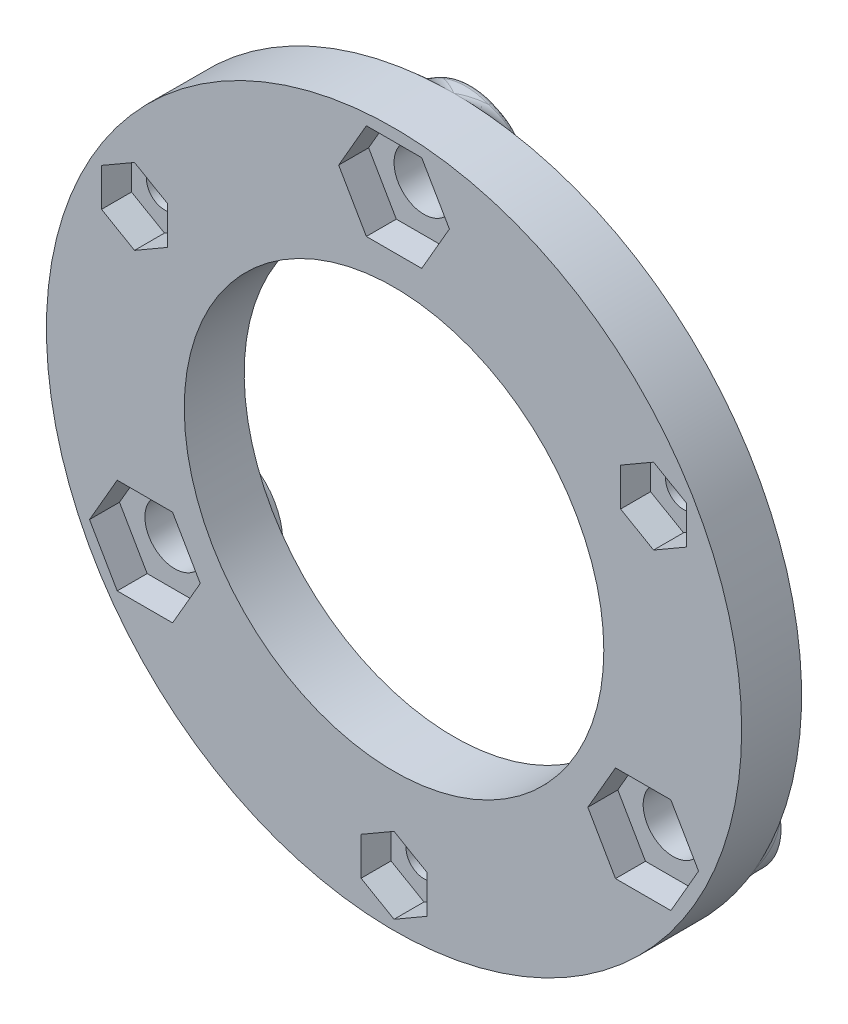
SolidWorks part; units mm, degrees
ref_plane "Front Plane" through (0, 0, 0) normal (0, 0, 1) x (1, 0, 0)
ref_plane "Top Plane" through (0, 0, 0) normal (0, 1, 0) x (1, 0, 0)
ref_plane "Right Plane" through (0, 0, 0) normal (1, 0, 0) x (0, 0, -1)
sketch "Sketch2" plane through (0, 0, 0) normal (0, 0, 1) x (1, 0, 0)
  line L0 (0, 24) -> (0, 0) construction
  line L1 (0, 0) -> (21.6506, 12.5) construction
  circle A0 centre (0, 0) radius 29
  circle A1 centre (0, 0) radius 17.5
  circle A2 centre (0, 0) radius 24 construction
  circle A3 centre (0, 24) radius 2.5
  circle A4 centre (0, 0) radius 25 construction
  circle A5 centre (20.7846, -12) radius 2.5
  circle A8 centre (21.6506, 12.5) radius 1.5
  circle A9 centre (0, -25) radius 1.5
  circle A11 centre (0, 0) radius 8 construction
  circle A14 centre (0, 24) radius 5 construction
  circle A15 centre (0, 0) radius 19 construction
  circle A16 centre (-20.7846, -12) radius 2.5
  circle A19 centre (-21.6506, 12.5) radius 1.5
  point P17 (0, 0)
  point P24 (0, 0)
  dimension "D1" = 58
  dimension "D2" = 48
  dimension "D4" = 5
  dimension "D7" = 3
  dimension "D3" = 16
  dimension "D10" = 10
  dimension "D5" = 4
  dimension "D9" = 1.5
  dimension "D11" = 60
  dimension "D6" = 3
  dimension "D8" = 3
extrude "Boss-Extrude1" add sketch "Sketch2" along normal blind 5
sketch "Sketch3" plane through (0, 0, 5) normal (0, 0, 1) x (1, 0, 0)
  line L0 (0, 24) -> (0, 0) construction
  line L13 (-4.6188, 24) -> (-2.3094, 20)
  line L14 (-2.3094, 20) -> (2.3094, 20)
  line L15 (2.3094, 20) -> (4.6188, 24)
  line L16 (4.6188, 24) -> (2.3094, 28)
  line L17 (2.3094, 28) -> (-2.3094, 28)
  line L18 (-2.3094, 28) -> (-4.6188, 24)
  line L20 (21.6506, 9.3246) -> (24.4006, 10.9123)
  line L21 (24.4006, 10.9123) -> (24.4006, 14.0877)
  line L22 (24.4006, 14.0877) -> (21.6506, 15.6754)
  line L23 (21.6506, 15.6754) -> (18.9006, 14.0877)
  line L24 (18.9006, 14.0877) -> (18.9006, 10.9123)
  line L25 (18.9006, 10.9123) -> (21.6506, 9.3246)
  circle A0 centre (0, 24) radius 4 construction
  circle A1 centre (21.6506, 12.5) radius 2.75 construction
  dimension "D1" = 8
  dimension "D2" = 5.5
extrude "Cut-Extrude1" cut sketch "Sketch3" against normal blind 2.5
pattern_circular "CirPattern1" count 3 over 360 about axis through (0, 0, 5) along (0, 0, -1) of "Cut-Extrude1" reverse direction yes
sketch "Sketch4" plane through (0, 0, 0) normal (0, 0, -1) x (-1, 0, 0)
  circle A0 centre (0, 24) radius 4
  circle A1 centre (0, 24) radius 5
  dimension "D1" = 8
extrude "Boss-Extrude2" add sketch "Sketch4" along normal blind 1.5
fillet "Fillet1" radius 1.5 1 edges at (-5, 24, 0)
fillet "Fillet2" radius 0.5 2 edges at (0, 29, -1.5) (0, 19, -1.5)
chamfer "Chamfer1" distance 0.25 angle 45 1 edges at (-4, 24, -1.5)
pattern_circular "CirPattern2" count 3 over 360 about axis through (0, 0, 5) along (0, 0, -1) of "Fillet1", "Boss-Extrude2", "Chamfer1" reverse direction yes
equation "\"Nr\"= \"Ns\" + 2 * \"Np\"'num teeth"
equation "\"module\"= 0.8"
equation "\"pressure_angle\"= 20deg"
equation "\"h_a\"= 1 * \"module\"'addendum"
equation "\"h_f\"= 1.25 * \"module\"'dedendum"
equation "\"clr_tip_root\"= \"h_f\" - \"h_a\"'clearance of gear tooth tip and root"
equation "\"dp_r\"= \"module\" * \"Nr\"'PCD"
equation "\"db_r\"= \"dp_r\" * cos ( \"pressure_angle\" )'base CD"
equation "\"fw_r\"= 11.5mm'face width"
equation "\"alpha_r\"= sqr ( \"dp_r\" ^ 2 - \"db_r\" ^ 2 ) / \"db_r\" * 180 / pi - \"pressure_angle\""
equation "\"beta_r\"= ( 360 / ( 4 * \"Nr\" ) + \"alpha_r\" ) * 2"
equation "\"bearing_ID\"= \"module\" * ( \"Ns\" + \"Np\" ) + 10"
equation "\"bearing_OD\"= 1.18 * \"bearing_ID\" + 8.57"
equation "\"bearing_height\"= 0.09 * \"bearing_ID\" + 4.62"
equation "\"clearance_planet\"=1.5"
equation "\"case_dist\"= \"sec_carrier_thickness\" + \"clearance_planet\" + \"sun_coupler_hub_thickness\" - \"case_mounting_surface_height\""
equation "\"Motor_case_OD_max\"= \"case_mounting_PCD\" + \"case_mounting_hole_allen_socket_dia\" + \"clearance_case_mount_holes_shell_thickness\" * 2"
equation "\"case_mounting_PCD\"= \"motor_case_OD_base\" + \"case_mounting_hole_shift\" * 2"
equation "\"bearing mount thickness\"= IIF((\"bearing_OD\" + \"output_mounting_hole_dia\" * 4) > (\"Nr\" * \"module\" + 2 * \"h_b\"), \"output_mounting_hole_dia\" * 2, ((\"Nr\" * \"module\" + 2 * \"h_b\" - (\"bearing_OD\" + \"output_mounting_hole_dia\" * 4)) / 2) + \"output_mounting_hole_dia\" * 2 + \"standard_clearance_1_5mm\")"
equation "\"case_mounting_hole_dia\"=3"
equation "\"output_mounting_PCD\"= \"bearing_OD\" + \"bearing mount thickness\""
equation "\"output_mounting_hole_dia\"= 4"
equation "\"clearance_case_mount_holes_shell_thickness\"= 1"
equation "\"motor_case_OD_base\"= \"motor_OD\" + \"clearance_motor_and_case\" * 2 + \"Motor_case_thickness\" * 2"
equation "\"sec_carrier_thickness\"= 5"
equation "\"sun_coupler_hub_thickness\"= 4"
equation "\"clearance_sun_coupler_sec_carrier\"= 1.5"
equation "\"clearance_motor_and_case\" = IIF(\"ring_OD\" < \"motor_OD\", 5, (\"ring_OD\" - \"motor_OD\")/2 + 5)"
equation "\"motor_OD\"= 88.6"
equation "\"Motor_case_thickness\"= 2.5"
equation "\"Motor_case_ID\"= \"motor_OD\" + \"clearance_motor_and_case\" * 2"
equation "\"case_mounting_hole_shift\"= \"case_mounting_hole_dia\" / 2 - 0.5"
equation "\"output_mounting_nut_wrench_size\"= 7"
equation "\"output_mounting_nut_thickness\"= 3.2"
equation "\"case_mounting_hole_allen_socket_dia\"= 5.5"
equation "\"output_mounting_nut_depth\"= 3"
equation "\"case_mounting_bolt_depth\"= 4.5"
equation "\"Ns\"= 20"
equation "\"Np\"= 40"
equation "\"ring_radial_thickness\"= 5"
equation "\"ring_OD\"= \"Nr\" * \"module\" + \"ring_radial_thickness\" * 2"
equation "\"ring_to_chamfer_clearance\"= 2"
equation "\"Motor_case_OD_base_to_chamfer\"=5"
equation "\"pattern_offset_from_motor_case_OD_base\"= 3"
equation "\"pattern_bulge_dia\"= 3"
equation "\"pattern_num_bulge\"= 18"
equation "\"pattern_depth\"= 2"
equation "\"motor_height\"= 43"
equation "\"case_mounting_wrench_size\"= 5.5"
equation "\"case_mounting_nut_clearance\"= 2"
equation "\"base_plate_thickness\"= 4"
equation "\"case_mounting_nut_thickness\"= 2.4"
equation "\"case_mounting_surface_height\"= 4"
equation "\"motor_mount_hole_PCD\"= 32"
equation "\"motor_mount_hole_dia\"= 4"
equation "\"motor_mount_hole_num\"= 4"
equation "\"central_hole_offset_from_motor_mount_PCD\"= 5"
equation "\"wire_slot_dist_from_center\"= 30"
equation "\"wire_slot_length\"= 10"
equation "\"wire_slot_radius\"= 4"
equation "\"driver_upper_holes_dist_from_center\"= 23"
equation "\"driver_lower_holes_dist_from_center\"= 15"
equation "\"driver_side_holes_dist_from_center\"= 20"
equation "\"driver_mount_holes_dia\"= 2.5"
equation "\"driver_mount_inserts_OD\"= 3.5"
equation "\"driver_mount_thickness\"= 1.5"
equation "\"driver_mount_height\"= 4"
equation "\"air_flow_hole_offset\"= 3"
equation "\"num_planet\"= 3"
equation "\"planet_pin_bolt_dia\"= 5"
equation "\"planet_pin_socket_head_dia\"= 8.5"
equation "\"carrier_PCD\"= ( \"Np\" + \"Ns\" ) * \"module\""
equation "\"D1@Sketch2\"=\"bearing_ID\""
equation "\"D2@Sketch2\"=\"carrier_PCD\""
equation "\"D4@Sketch2\"=\"planet_pin_bolt_dia\""
equation "\"D6@Sketch2\"=\"num_planet\""
equation "\"D8@Sketch2\"=\"num_planet\""
equation "\"D1@CirPattern1\"=\"num_planet\""
equation "\"planet_shaft_dia\"= 8"
equation "\"fw_p\"= \"fw_r\""
equation "\"planet_shaft_step_offset\"= 1"
equation "\"carrier_trapezoidal_support_sun_offset\"= 5"
equation "\"carrier_trapezoidal_support_hole_PCD_offset_bearing_ID\"= 4"
equation "\"carrier_trapezoidal_support_hole_dia\"= 3"
equation "\"carrier_trapezoidal_support_hole_socket_head_dia\"= 5.5"
equation "\"carrier_bearing_step_width\"= 1.5"
equation "\"standard_clearance_1_5mm\"=1.5"
equation "\"standard_fillet_1_5mm\"= 1.5"
equation "\"sun_shaft_bearing_OD\"= 16"
equation "\"sun_shaft_bearing_width\"= 4"
equation "\"standard_bearing_insertion_chamfer\"= 0.5"
equation "\"D7@Sketch2\"=\"carrier_trapezoidal_support_hole_dia\""
equation "\"D5@Sketch2\"=\"carrier_trapezoidal_support_hole_PCD_offset_bearing_ID\""
equation "\"D3@Sketch2\"=\"Ns\"*\"module\""
equation "\"carrier_trapezoidal_support_hole_wrench_size\"= 5.5"
equation "\"planet_pin_bolt_wrench_size\"= 8"
equation "\"D1@Boss-Extrude1\"=\"sec_carrier_thickness\""
equation "\"D1@Cut-Extrude1\"=\"sec_carrier_thickness\"/2"
equation "\"D1@Sketch4\"=\"planet_shaft_dia\""
equation "\"D2@Sketch4\"=\"planet_shaft_step_offset\""
equation "\"D1@Boss-Extrude2\"=\"clearance_planet\""
equation "\"D1@Fillet1\"=\"standard_fillet_1_5mm\""
equation "\"D1@Chamfer1\"=\"standard_bearing_insertion_chamfer\"/2"
equation "\"D1@Fillet2\"=\"standard_fillet_1_5mm\"/3"
equation "\"D1@CirPattern2\"=\"num_planet\""
equation "\"D10@Sketch2\"=\"planet_shaft_dia\"+\"planet_shaft_step_offset\"*2"
equation "\"D9@Sketch2\"=\"standard_clearance_1_5mm\""
equation "\"D1@Sketch3\"=\"planet_pin_bolt_wrench_size\""
equation "\"D11@Sketch2\"=180/\"num_planet\""
equation "\"D2@Sketch3\"=\"carrier_trapezoidal_support_hole_wrench_size\""
equation "\"pressure angle\"= 20deg"
equation "\"motor_output_hole_PCD\"= 23"
equation "\"motor_output_hole_dia\"= 4"
equation "\"motor_output_hole_num\"= 4"
equation "\"h_b\"= 1.25 * \"module\"'dedendum"
equation "\"dp_s\"= \"module\" * \"Ns\"'PCD"
equation "\"db_s\"= \"dp_s\" * cos ( \"pressure angle\" )'base CD"
equation "\"fw_s_calc\"= 13mm'face width"
equation "\"alpha_s\"= sqr ( \"dp_s\" ^ 2 - \"db_s\" ^ 2 ) / \"db_s\" * 180 / pi - \"pressure angle\""
equation "\"beta_s\"= ( 360 / ( 4 * \"Ns\" ) - \"alpha_s\" ) * 2"
equation "\"dp_p\"= \"module\" * \"Np\"'PCD"
equation "\"db_p\"= \"dp_p\" * cos ( \"pressure angle\" )'base CD"
equation "\"alpha_p\"= sqr ( \"dp_p\" ^ 2 - \"db_p\" ^ 2 ) / \"db_p\" * 180 / pi - \"pressure angle\""
equation "\"beta_p\"= ( 360 / ( 4 * \"Np\" ) - \"alpha_p\" ) * 2"
equation "\"planet_bearing_OD\"= 12"
equation "\"planet_bearing_width\"= 3"
equation "\"planet_bore\"= 10"
equation "\"sun_shaft_bearing_ID\"= 8"
equation "\"sun_hub_dia\"= \"motor_output_hole_PCD\" + \"motor_output_hole_dia\" + \"standard_clearance_1_5mm\" * 4"
equation "\"sun_central_bolt_dia\"= 5"
equation "\"sun_central_bolt_socket_head_dia\"= 8.5"
equation "\"fw_s_used\"= \"fw_p\" + \"clearance_planet\" + \"sec_carrier_thickness\" + \"standard_clearance_1_5mm\""
equation "\"motor_output_hole_CSK_OD\"= 9'8.96 is exact value"
equation "\"motor_output_hole_CSK_head_height\"= 2.5"
equation "\"bearing_retainer_thickness\"= 2"
